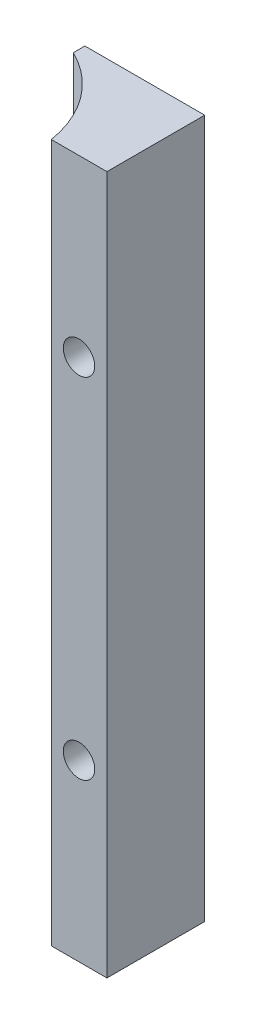
SolidWorks part; units mm, degrees
ref_plane "Front" through (0, 0, 0) normal (0, 0, 1) x (1, 0, 0)
ref_plane "Top" through (0, 0, 0) normal (0, 1, 0) x (1, 0, 0)
ref_plane "Right" through (0, 0, 0) normal (1, 0, 0) x (0, 0, -1)
sketch "Sketch1" plane through (0, 0, 0) normal (0, 1, 0) x (1, 0, 0)
  line L0 (0, 0) -> (0, 8.4)
  line L1 (0, 8.4) -> (-10.2923, 8.4)
  line L2 (-10.2923, 8.4) -> (-10.2923, 7.4)
  line L3 (-4.78, 0) -> (0, 0)
  arc A0 (-10.2923, 7.4) -> (-4.78, 0) centre (-14.6512, -1.6) cw
  dimension "D3" = 10
  dimension "D1" = 4.78
  dimension "D2" = 8.4
  dimension "D4" = 1.6
  dimension "D5" = 1
extrude "Boss-Extrude1" add sketch "Sketch1" along normal blind 60
sketch "Sketch2" plane through (0, 0, 0) normal (0, 0, 1) x (1, 0, 0)
  line L0 (-2.4, 60) -> (-2.4, 0) construction
  line L1 (-4.78, 60) -> (0, 60) construction
  line L2 (-4.78, 0) -> (0, 0) construction
  line L3 (-4.78, 60) -> (-4.78, 0) construction
  point P6 (-2.4, 45)
  point P7 (-2.4, 15)
  dimension "D1" = 15
  dimension "D2" = 15
  dimension "D3" = 2.38
hole_wizard "Ø2.7 (2.7) Diameter Hole1" positions "3DSketch1" profile "Sketch3" hole size "Ø2.7" standard "ANSI Metric" end condition up to next
sketch3d "3DSketch1"
  point P0 (-2.4, 45, 0)
  point P3 (-2.4, 15, 0)
sketch "Sketch3" plane through (-2.4, 45, 0) normal (1, 0, 0) x (0, -1, 0)
  line L0 (0, 0) -> (0, 8.4)
  line L1 (0, 8.4) -> (1.35, 8.4)
  line L2 (1.35, 8.4) -> (1.35, 0)
  line L5 (1.35, 0) -> (0, 0)
  line L11 (0, -6.35) -> (0, 107.95) construction
  dimension "Thru Hole Dia." = 2.7
  dimension "Thru Hole Depth" = 8.4
